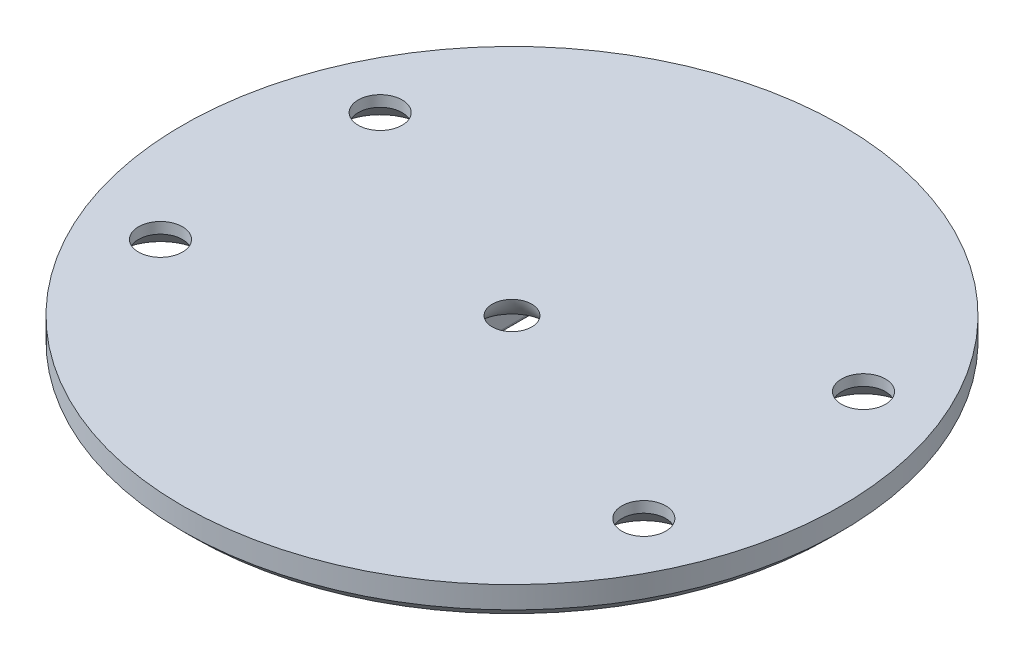
SolidWorks part; units mm, degrees
ref_plane "Front plane" through (0, 0, 0) normal (0, 0, 1) x (1, 0, 0)
ref_plane "Top plane" through (0, 0, 0) normal (0, 1, 0) x (1, 0, 0)
ref_plane "Right plane" through (0, 0, 0) normal (1, 0, 0) x (0, 0, -1)
ref_axis "Axis X" through (0, 0, 0) along (1, 0, 0)
ref_axis "Axis Y" through (0, 0, 0) along (0, 1, 0)
ref_axis "Axis Z" through (0, 0, 0) along (0, 0, 1)
sketch "Sketch1" plane through (0, 0, 0) normal (0, 1, 0) x (1, 0, 0)
  circle A0 centre (0, 0) radius 15
  dimension "D1" = 30
extrude "Extrude1" add sketch "Sketch1" along normal blind 1.5
sketch "Sketch2" plane through (0, 1.5, 0) normal (0, 1, 0) x (1, 0, 0)
  circle A0 centre (0, 0) radius 2.45
  dimension "D1" = 4.9
extrude "Extrude3" [suppressed] add sketch "Sketch2" along normal blind 13
sketch "Sketch5" plane through (0, 0, 0) normal (0, -1, 0) x (1, 0, 0)
  line L0 (-3.4713, 0) -> (3.4713, 0) construction
  line L1 (0, 5) -> (0, -5) construction
  line L2 (-3.4713, 8) -> (-6.4713, 8)
  line L3 (-3.4713, 8) -> (-3.4713, -8)
  line L4 (-3.4713, -8) -> (-6.4713, -8)
  line L5 (-6.4713, 8) -> (-6.4713, -8)
  line L6 (-3.4713, 8) -> (-6.4713, -8) construction
  line L7 (-3.4713, -8) -> (-6.4713, 8) construction
  line L8 (3.4713, -8) -> (6.4713, -8)
  line L9 (6.4713, 8) -> (6.4713, -8)
  line L10 (3.4713, 8) -> (6.4713, 8)
  line L11 (3.4713, 8) -> (3.4713, -8)
  point P4 (0, 0)
  point P6 (-4.9713, 0)
  dimension "D1" = 6.9426
  dimension "D2" = 3
  dimension "D3" = 16
extrude "Extrude4" add sketch "Sketch5" along normal blind 3 draft 10 and the other way blind 1
fillet "Fillet1" radius 0.25 14 edges at (-4.9713, -3, 7.471) (-4.0003, -3, 0) (-4.9713, -3, -7.471) (-5.9423, -3, 0) (4.9713, -3, 7.471) (5.9423, -3, 0) (4.9713, -3, -7.471) (4.0003, -3, 0) (4.9713, 0, 8) (4.9713, 0, -8) (-4.9713, 0, -8) (-4.9713, 0, 8) (3.4713, 0, 0) (-3.4713, 0, 0)
fillet "Fillet2" radius 1 2 edges at (6.4713, 0, 0) (-6.4713, 0, 0)
sketch "Sketch7" plane through (0, 0, 0) normal (0, -1, 0) x (1, 0, 0)
  line L1 (11, 5) -> (-11, 5) construction
  line L2 (11, 5) -> (11, -5) construction
  line L3 (11, -5) -> (-11, -5) construction
  line L4 (-11, 5) -> (-11, -5) construction
  line L5 (11, 5) -> (-11, -5) construction
  line L6 (11, -5) -> (-11, 5) construction
  circle A0 centre (-11, 5) radius 1
  circle A1 centre (11, 5) radius 1
  circle A2 centre (11, -5) radius 1
  circle A3 centre (-11, -5) radius 1
  point P0 (0, 0)
  dimension "D3" = 2
  dimension "D4" = 2
  dimension "D5" = 2
  dimension "D6" = 2
  dimension "D1" = 22
  dimension "D2" = 10
extrude "Extrude5" cut sketch "Sketch7" against normal through all
chamfer "Chamfer3" distance 1 angle 45 4 edges at (11, 0, -6) (11, 0, 4) (-11, 0, -6) (-11, 0, 4)
sketch "Sketch8" plane through (0, 0, 0) normal (0, -1, 0) x (1, 0, 0)
  circle A0 centre (0, 0) radius 5 construction
  circle A1 centre (0, 5) radius 1.1
  circle A2 centre (5, 0) radius 1.1
  circle A3 centre (0, -5) radius 1.1
  circle A4 centre (-5, 0) radius 1.1
  dimension "D1" = 10
  dimension "D2" = 2.2
  dimension "D3" = 4
extrude "Extrude6" [suppressed] cut sketch "Sketch8" against normal through all
chamfer "Chamfer2" [suppressed] distance 1 angle 45
chamfer "Chamfer4" distance 0.5 angle 45 1 edges at (0, 0, 15)
sketch "Sketch9" [suppressed] plane through (0, 14.5, 0) normal (0, 1, 0) x (1, 0, 0)
  circle A0 centre (0, 0) radius 2.45
  dimension "D1" = 4.9
extrude "Extrude7" [suppressed] add sketch "Sketch9" along normal blind 3 draft 1.5 draft outward yes
sketch "Sketch10" plane through (0, 0, 0) normal (0, -1, 0) x (1, 0, 0)
  circle A0 centre (0, 0) radius 0.9
  dimension "D1" = 1.8
extrude "Extrude8" cut sketch "Sketch10" against normal through all
fillet "Fillet3" [suppressed] radius 1
fillet "Fillet4" radius 2 1 edges at (0, 0, -0.9)
chamfer "Chamfer5" [suppressed] distance 0.2 angle 45
equation "\"motor_D\"= 30'Motor diameter"
equation "\"motor_H\"= 13'Motor heigh"
equation "\"motor_d1\"= 25.4558'Seating diameter of screws on the fixed part of the motor"
equation "\"motor_s1\"= 2'Screws diameter on the fixed part of motor"
equation "\"motor_s2\"= 2'Screws diameter on the moving part of motor"
equation "\"motor_Dc\"= 5'Central hole diameter of motor"
equation "\"bearing_d1\"= 8'Bearing inner diameter"
equation "\"bearing_d2\"= 16'Bearing external diameter"
equation "\"bearing h\"= 5'Bearing heigh"
equation "\"pin_d\"= 2'Pin diameter"
equation "\"pin_h\"= 12'Pin heigh"
equation "\"magnet_d1\"= 5'Magnet inner diameter"
equation "\"magnet_d2\"= 9.5'Magnet external diameter"
equation "\"magnet_h\"= 3'Magnet heigh"
equation "\"D1@Sketch1\"= IIF ( \"motor_d2\" = 0 , \"motor_D\" , \"motor_d2\" + \"motor_s2\" * 2 + 2 )"
equation "\"D1@Extrude3\"=\"motor_H\""
equation "\"D1@Sketch5\"=\"pin_d\"+6-(\"pin_d\"+1)*tan(10*3.14/180)*2"
equation "\"D3@Sketch5\"=\"pin_h\"+4"
equation "\"D1@Extrude4\"=\"pin_d\"+1"
equation "\"motor_a2\"= 10'Seating parameter in rectangle of screws on the moving part of the motor"
equation "\"motor_b2\"= 22'Seating parameter in rectangle of screws on the moving part of the motor"
equation "\"D1@Sketch7\"=if(\"motor_a2\">\"motor_b2\",\"motor_a2\",\"motor_b2\")"
equation "\"D2@Sketch7\"=if(\"motor_a2\">\"motor_b2\",\"motor_b2\",\"motor_a2\")"
equation "\"D3@Sketch7\"=\"motor_s2\""
equation "\"motor_d2\"= 0'Seating diameter of screws on the moving part of the motor (if this parameter is not determine, write 0)"
equation "\"D4@Sketch7\"=\"D3@Sketch7\""
equation "\"D5@Sketch7\"=\"D3@Sketch7\""
equation "\"D6@Sketch7\"=\"D3@Sketch7\""
equation "\"Extrude5\"= IIF ( \"motor_d2\" = 0 , \"unsuppressed\" , \"suppressed\" )"
equation "\"D1@Sketch8\"=if( \"motor_d2\"=0,10,\"motor_d2\")"
equation "\"D2@Sketch8\"=\"motor_s2\"+\"print_offset\""
equation "\"Extrude6\"= IIF ( \"motor_d2\" = 0 , \"suppressed\" , \"unsuppressed\" )"
equation "\"Chamfer3\"= IIF ( \"motor_d2\" = 0 , \"unsuppressed\" , \"suppressed\" )"
equation "\"Chamfer2\"= IIF ( \"motor_d2\" = 0 , \"suppressed\" , \"unsuppressed\" )"
equation "\"D1@Sketch9\"=if( \"magnet_d1\"=0,\"motor_Dc\",\"magnet_d1\")-\"print_offset\"/2"
equation "\"D1@Extrude7\"=\"magnet_h\""
equation "\"Extrude7\"= IIF ( \"motor_cmh\" = 0 , \"unsuppressed\" , \"suppressed\" )"
equation "\"motor_cmd\"= 12'Central magnet mount diameter"
equation "\"motor_cmh\"= 1.4'Central magnet mount heigh (if not write 0)"
equation "\"motor_whR\"= 10'Distance from center of motor to wires"
equation "\"print_offset\"= 0.2'Offset for printing holes"
equation "\"D1@Sketch10\"=2-\"print_offset\""
equation "\"D1@Sketch2\"=\"motor_Dc\"-\"print_offset\"/2"
equation "\"Fillet3\"= IIF ( \"motor_cmh\" = 0 , \"unsuppressed\" , \"suppressed\" )"
equation "\"Extrude3\"= IIF ( \"motor_cmh\" = 0 , \"unsuppressed\" , \"suppressed\" )"
